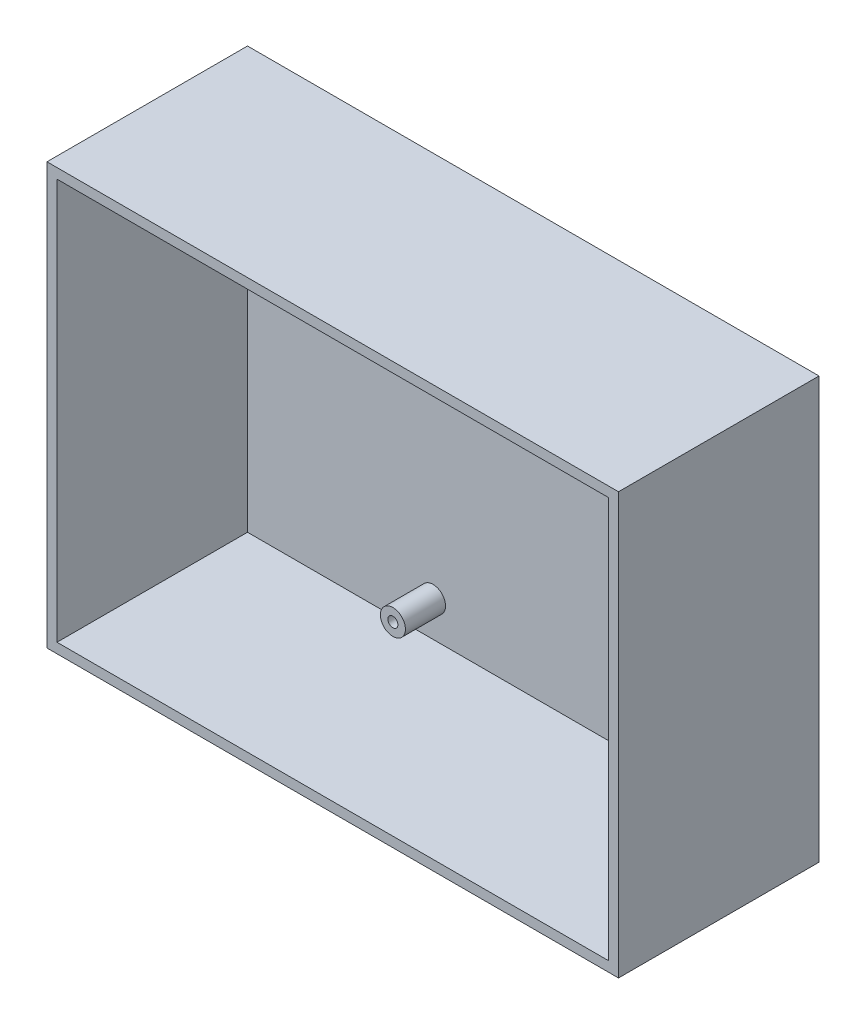
SolidWorks part; units mm, degrees
ref_plane "Спереди" through (0, 0, 0) normal (0, 0, 1) x (1, 0, 0)
ref_plane "Сверху" through (0, 0, 0) normal (0, 1, 0) x (1, 0, 0)
ref_plane "Справа" through (0, 0, 0) normal (1, 0, 0) x (0, 0, -1)
sketch "Эскиз1" plane through (0, 0, 0) normal (0, 0, 1) x (1, 0, 0)
  line L1 (-55, 40) -> (55, 40)
  line L2 (-55, 40) -> (-55, -40)
  line L3 (-55, -40) -> (55, -40)
  line L4 (55, 40) -> (55, -40)
  line L5 (-55, 40) -> (55, -40) construction
  line L6 (-55, -40) -> (55, 40) construction
  point P0 (0, 0)
  dimension "D1" = 80
  dimension "D2" = 110
extrude "Вытянуть-Тонкостенный1" add sketch "Эскиз1" along normal blind 38 thin thin type one direction wall 2
sketch "Эскиз2" plane through (0, 0, 0) normal (0, 0, -1) x (-1, 0, 0)
  line L0 (57, 42) -> (57, -42) construction
  line L1 (-57, 42) -> (57, 42) construction
  line L2 (-57, -42) -> (-57, 42) construction
  line L3 (57, -42) -> (-57, -42) construction
  line L4 (57, 42) -> (57, -42)
  line L5 (-57, 42) -> (57, 42)
  line L6 (-57, -42) -> (-57, 42)
  line L7 (57, -42) -> (-57, -42)
extrude "Бобышка-Вытянуть1" add sketch "Эскиз2" along normal blind 2
ref_plane "Плоскость1" through (0, 0, 8) normal (0, 0, 1) x (1, 0, 0)
sketch "Эскиз3" plane through (0, 0, 8) normal (0, 0, 1) x (1, 0, 0)
  line L0 (55, -40) -> (55, 40) construction
  line L1 (50, -35) -> (-20, -35) construction
  line L2 (50, -35) -> (50, 15) construction
  line L3 (50, 15) -> (-20, 15) construction
  line L4 (-20, -35) -> (-20, 15) construction
  line L5 (-33.1063, -10) -> (53.7568, -10) construction
  line L6 (15, 25.5544) -> (15, -36.7248) construction
  line L7 (-55, -40) -> (55, -40) construction
  circle A0 centre (-18, 13) radius 1
  circle A1 centre (-18, 13) radius 2.5
  circle A2 centre (48, 13) radius 2.5
  circle A3 centre (48, 13) radius 1
  circle A4 centre (-18, 13) radius 1
  circle A5 centre (-18, 13) radius 2.5
  circle A6 centre (48, 13) radius 2.5
  circle A7 centre (48, 13) radius 1
  circle A8 centre (48, -33) radius 1
  circle A9 centre (48, -33) radius 2.5
  circle A10 centre (-18, -33) radius 2.5
  circle A11 centre (-18, -33) radius 1
  circle A12 centre (48, -33) radius 1
  circle A13 centre (48, -33) radius 2.5
  circle A14 centre (-18, -33) radius 2.5
  circle A15 centre (-18, -33) radius 1
  point P0 (15, -10)
  point P33 (0, 0)
  point P34 (0, 0)
  point P35 (15, 15)
  point P36 (-20, -10)
  point P39 (-17.0756, 13.2328)
  dimension "D5" = 2
  dimension "D6" = 5
  dimension "D1" = 50
  dimension "D2" = 70
  dimension "D3" = 5
  dimension "D4" = 5
  dimension "D7" = 46
  dimension "D8" = 66
extrude "Бобышка-Вытянуть2" add sketch "Эскиз3" against normal up to surface (8 mm away) contours A1 | A10 | A11 | A2 | A3 | A9 | A8 | A0 up to face at (0, 0, 0)
